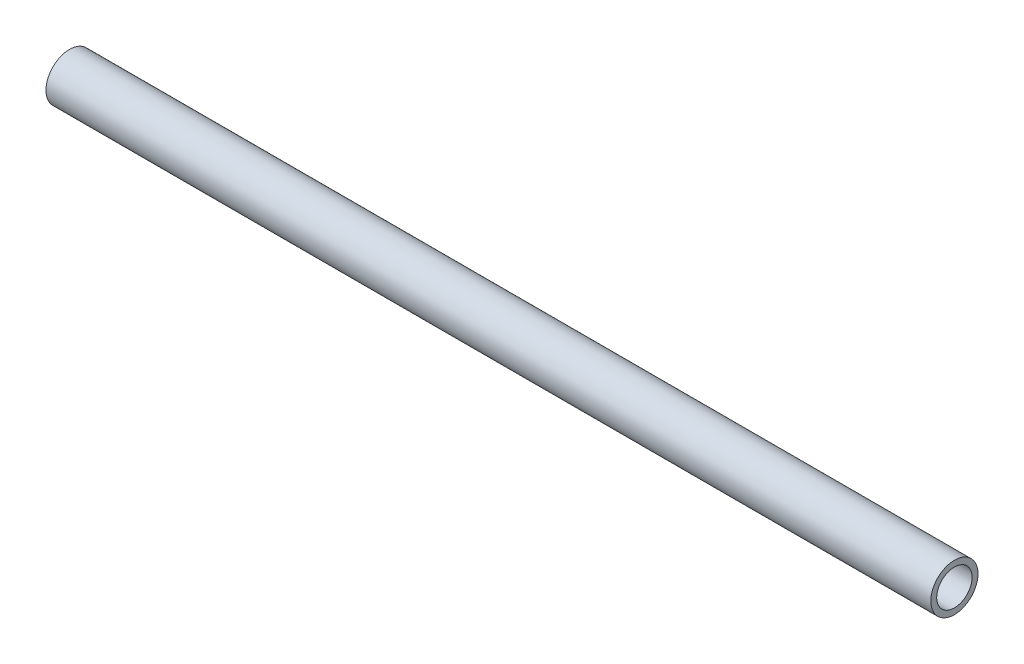
SolidWorks part; units mm, degrees
ref_plane "Piano frontale" through (0, 0, 0) normal (0, 0, 1) x (1, 0, 0)
ref_plane "Piano superiore" through (0, 0, 0) normal (0, 1, 0) x (1, 0, 0)
ref_plane "Piano destro" through (0, 0, 0) normal (1, 0, 0) x (0, 0, -1)
sketch "Schizzo2" plane through (0, 0, 0) normal (1, 0, 0) x (0, 0, -1)
  circle A0 centre (0, 0) radius 8
extrude "Estrusione-Sottile1" add sketch "Schizzo2" along normal mid plane 300 thin thin type one direction reverse wall 2
ref_point "Punto1"
ref_axis "Assi1" through (150, 0, 0) along (-1, 0, 0)
